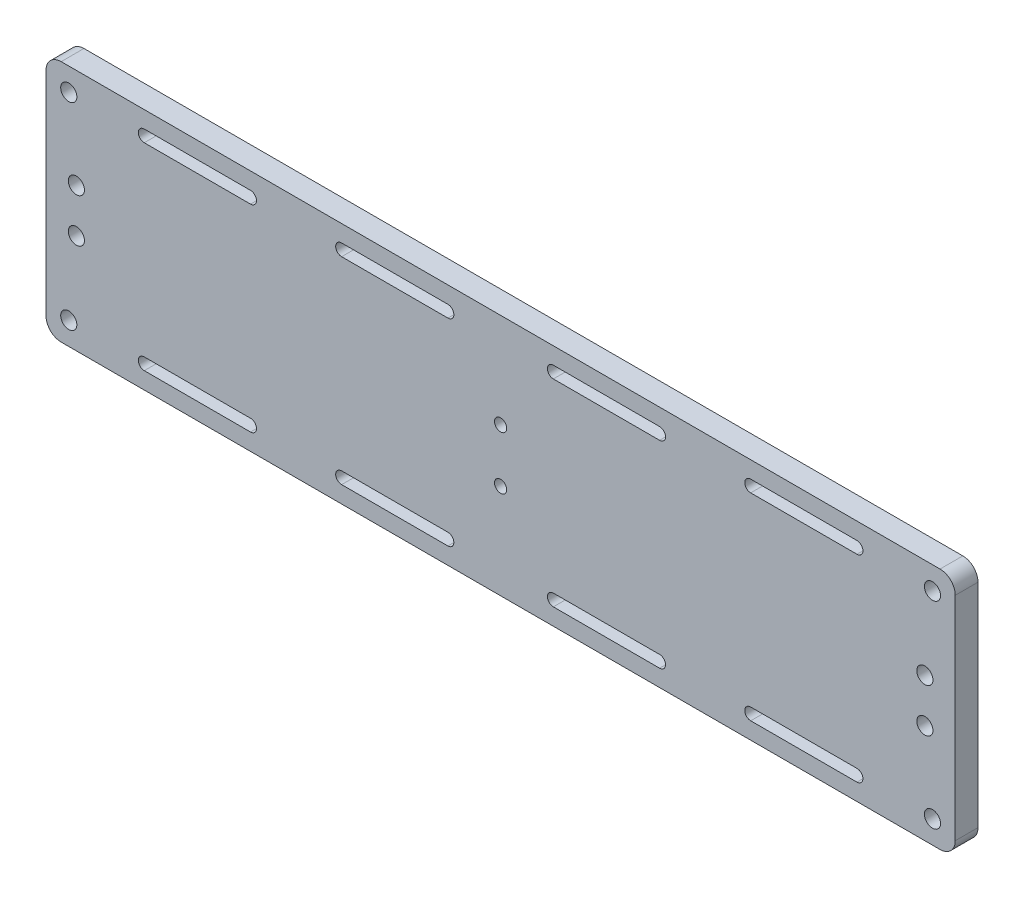
SolidWorks part; units mm, degrees
ref_plane "Front Plane" through (0, 0, 0) normal (0, 0, 1) x (1, 0, 0)
ref_plane "Top Plane" through (0, 0, 0) normal (0, 1, 0) x (1, 0, 0)
ref_plane "Right Plane" through (0, 0, 0) normal (1, 0, 0) x (0, 0, -1)
sketch "Sketch1" plane through (0, 0, 0) normal (0, 0, 1) x (1, 0, 0)
  line L1 (-190.1444, 50.8) -> (190.1444, 50.8)
  line L2 (-190.1444, 50.8) -> (-190.1444, -50.8)
  line L3 (-190.1444, -50.8) -> (190.1444, -50.8)
  line L4 (190.1444, 50.8) -> (190.1444, -50.8)
  line L5 (-190.1444, 50.8) -> (190.1444, -50.8) construction
  line L6 (-190.1444, -50.8) -> (190.1444, 50.8) construction
  point P0 (0, 0)
  dimension "D1" = 101.6
  dimension "D2" = 380.2888
extrude "Boss-Extrude1" add sketch "Sketch1" along normal blind 9.525 contours L1 L4 L3 L2
hole_wizard "#10 Clearance Slot1" positions "Sketch3" profile "Sketch2" size "#10" standard "ANSI Inch" slot yes end condition through all
sketch "Sketch3" plane through (0, 0, 9.525) normal (0, 0, 1) x (1, 0, 0)
  line L0 (-151.5364, -41.275) -> (-102.108, -41.275) construction
  line L2 (-126.8222, 41.275) -> (-44.2722, 41.275)
  line L3 (-126.8222, 41.275) -> (-126.8222, -41.275)
  line L4 (-126.8222, -41.275) -> (-44.2722, -41.275)
  line L5 (-44.2722, 41.275) -> (-44.2722, -41.275)
  line L6 (-126.8222, 41.275) -> (-44.2722, -41.275) construction
  line L7 (-126.8222, -41.275) -> (-44.2722, 41.275) construction
  line L9 (44.2722, 41.275) -> (126.8222, 41.275)
  line L10 (44.2722, 41.275) -> (44.2722, -41.275)
  line L11 (44.2722, -41.275) -> (126.8222, -41.275)
  line L12 (126.8222, 41.275) -> (126.8222, -41.275)
  line L13 (44.2722, 41.275) -> (126.8222, -41.275) construction
  line L14 (44.2722, -41.275) -> (126.8222, 41.275) construction
  line L15 (-85.5472, 0) -> (85.5472, 0) construction
  point P0 (-126.8222, -41.275)
  point P4 (-44.2722, -41.275)
  point P6 (44.2722, -41.275)
  point P8 (126.8222, -41.275)
  point P10 (126.8222, 41.275)
  point P12 (44.2722, 41.275)
  point P14 (-44.2722, 41.275)
  point P16 (-126.8222, 41.275)
  dimension "D1" = 49.4284
  dimension "D2" = 82.55
  dimension "D3" = 82.55
  dimension "D4" = 171.0944
sketch "Sketch2" plane through (-126.8222, -41.275, 9.525) normal (1, 0, 0) x (0, -1, 0)
  line L0 (0, 0) -> (0, 9.525)
  line L1 (0, 9.525) -> (2.4892, 9.525)
  line L2 (2.4892, 9.525) -> (2.4892, 0)
  line L5 (2.4892, 0) -> (0, 0)
  line L11 (0, -6.35) -> (0, 107.95) construction
  dimension "Thru Hole Dia." = 4.9784
  dimension "Thru Hole Depth" = 9.525
fillet "Fillet1" radius 6.35 4 edges at (-190.1444, 50.8, 4.7625) (-190.1444, -50.8, 4.7625) (190.1444, 50.8, 4.7625) (190.1444, -50.8, 4.7625)
sketch "Sketch6" plane through (0, 0, 0) normal (0, 0, -1) x (-1, 0, 0)
  line L0 (-190.1444, 0) -> (190.1444, 0) construction
  line L1 (-190.1444, 44.45) -> (-190.1444, -44.45) construction
  line L2 (190.1444, 44.45) -> (190.1444, -44.45) construction
  line L3 (0, 50.8) -> (0, -50.8) construction
  line L4 (183.7944, 50.8) -> (-183.7944, 50.8) construction
  line L5 (183.7944, -50.8) -> (-183.7944, -50.8) construction
  point P12 (-177.4444, 9.144)
  point P13 (-177.4444, -9.144)
  point P17 (177.4444, 9.144)
  point P18 (177.4444, -9.144)
  dimension "D1" = 18.288
  dimension "D2" = 9.144
  dimension "D3" = 12.7
hole_wizard "CBORE for 1/4 Socket Head Cap Screw4" positions "Sketch14" profile "Sketch15" counterbore size "1/4" standard "ANSI Inch" end condition through all
sketch "Sketch14" plane through (0, 0, 0) normal (0, 0, -1) x (-1, 0, 0)
  point P0 (-177.4444, 9.144)
  point P3 (-177.4444, -9.144)
  point P6 (177.4444, 9.144)
  point P9 (177.4444, -9.144)
sketch "Sketch15" plane through (177.4444, 9.144, 0) normal (1, 0, 0) x (0, 1, 0)
  line L0 (0, 0) -> (0, 9.525)
  line L1 (0, 9.525) -> (3.3782, 9.525)
  line L3 (3.3782, 9.525) -> (3.3782, 3.175)
  line L4 (3.3782, 3.175) -> (5.5562, 3.175)
  line L5 (5.5562, 3.175) -> (5.5562, 0)
  line L7 (5.5562, 0) -> (0, 0)
  line L11 (0, -6.35) -> (0, 107.95) construction
  dimension "Thru Hole Dia." = 6.7564
  dimension "Thru Hole Depth" = 9.525
  dimension "C'Bore Dia." = 11.1125
  dimension "C'Bore Depth" = 3.175
sketch "Sketch18" plane through (0, 0, 0) normal (0, 0, -1) x (-1, 0, 0)
  line L0 (0, 50.8) -> (0, -50.8) construction
  point P0 (0, 11.1125)
  point P1 (0, -11.1125)
  point P4 (-1.9718, -89.2799)
  dimension "D1" = 22.225
  dimension "D2" = 11.1125
hole_wizard "CBORE for #10 Socket Head Cap Screw1" positions "Sketch19" profile "Sketch20" counterbore size "#10" standard "ANSI Inch" end condition through all
sketch "Sketch19" plane through (0, 0, 0) normal (0, 0, -1) x (-1, 0, 0)
  point P0 (0, 11.1125)
  point P3 (0, -11.1125)
sketch "Sketch20" plane through (0, 11.1125, 0) normal (1, 0, 0) x (0, 1, 0)
  line L0 (0, 0) -> (0, 9.525)
  line L1 (0, 9.525) -> (2.5527, 9.525)
  line L3 (2.5527, 9.525) -> (2.5527, 2.54)
  line L4 (2.5527, 2.54) -> (4.064, 2.54)
  line L5 (4.064, 2.54) -> (4.064, 0)
  line L7 (4.064, 0) -> (0, 0)
  line L11 (0, -6.35) -> (0, 107.95) construction
  dimension "Thru Hole Dia." = 5.1054
  dimension "Thru Hole Depth" = 9.525
  dimension "C'Bore Dia." = 8.128
  dimension "C'Bore Depth" = 2.54
sketch "Sketch21" plane through (0, 0, 0) normal (0, 0, -1) x (-1, 0, 0)
  line L0 (190.1444, 44.45) -> (190.1444, -44.45) construction
  line L1 (183.7944, 50.8) -> (-183.7944, 50.8) construction
  line L2 (183.7944, -50.8) -> (-183.7944, -50.8) construction
  line L3 (-190.1444, 44.45) -> (-190.1444, -44.45) construction
  point P0 (180.6194, 41.275)
  point P1 (180.6194, -41.275)
  point P2 (-180.6194, 41.275)
  point P3 (-180.6194, -41.275)
  dimension "D1" = 9.525
  dimension "D2" = 9.525
  dimension "D3" = 9.525
  dimension "D4" = 9.525
hole_wizard "CBORE for 1/4 Binding Head Machine Screw1" positions "Sketch22" profile "Sketch23" counterbore size "1/4" standard "ANSI Inch"
sketch "Sketch22" plane through (0, 0, 0) normal (0, 0, -1) x (-1, 0, 0)
  point P0 (180.6194, 41.275)
  point P3 (180.6194, -41.275)
  point P6 (-180.6194, 41.275)
  point P9 (-180.6194, -41.275)
sketch "Sketch23" plane through (-180.6194, 41.275, 0) normal (1, 0, 0) x (0, 1, 0)
  line L0 (0, 0) -> (0, 12.827)
  line L1 (0, 12.827) -> (3.3782, 12.827)
  line L2 (3.3782, 12.827) -> (3.3782, 3.175)
  line L3 (3.3782, 3.175) -> (5.5562, 3.175)
  line L4 (5.5562, 3.175) -> (5.5562, 0)
  line L5 (5.5562, 0) -> (0, 0)
  line L10 (0, 12.827) -> (-3.3782, 12.827) construction
  line L11 (0, -6.35) -> (0, 107.95) construction
  dimension "Hole Dia." = 6.7564
  dimension "Hole Depth" = 12.827
  dimension "C'Bore Dia." = 11.1125
  dimension "C'Bore Depth" = 3.175
  dimension "Drill Angle" = 180
equation "\"outer tube diameter\"= 4.486"
equation "\"Mounting screw spacing\"= 3.25"
equation "\"distance between tubes min\"= .5"
equation "\"D2@Sketch1\"=2*\"outer tube diameter\"+\"distance between tubes min\"+\"distance between tube max\" + 1.5in"
equation "\"distance between tube max\"= 4"
equation "\"D4@Sketch3\"=\"outer tube diameter\"+(\"distance between tube max\"+\"distance between tubes min\")/2"
